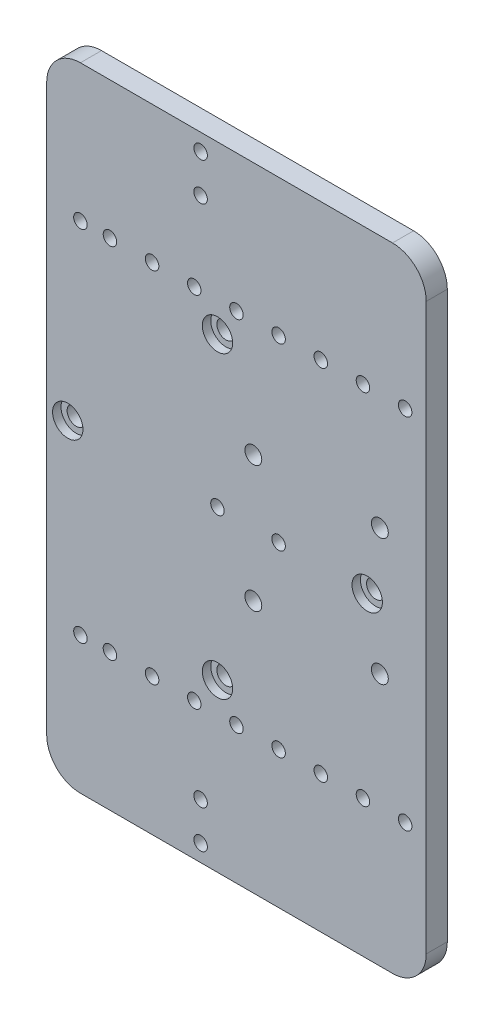
SolidWorks part; units mm, degrees
ref_plane "前视基准面" through (0, 0, 0) normal (0, 0, 1) x (1, 0, 0)
ref_plane "上视基准面" through (0, 0, 0) normal (0, 1, 0) x (1, 0, 0)
ref_plane "右视基准面" through (0, 0, 0) normal (1, 0, 0) x (0, 0, -1)
sketch "草图1" plane through (0, 0, 0) normal (0, 0, 1) x (1, 0, 0)
  line L1 (0, 0) -> (90, 0)
  line L2 (0, 0) -> (0, -150)
  line L3 (0, -150) -> (90, -150)
  line L4 (90, 0) -> (90, -150)
  circle A4 centre (79, -60) radius 2
  circle A5 centre (79, -90) radius 2
  circle A12 centre (49, -60) radius 2
  circle A13 centre (49, -90) radius 2
  circle A14 centre (40.5, -39.5) radius 2.15
  circle A15 centre (40.5, -110.5) radius 2.15
  circle A16 centre (76, -75) radius 2.15
  circle A17 centre (5, -75) radius 2.15
  circle A18 centre (85, -117.5) radius 1.6
  circle A19 centre (75, -117.5) radius 1.6
  circle A20 centre (65, -117.5) radius 1.6
  circle A21 centre (55, -117.5) radius 1.6
  circle A22 centre (45, -117.5) radius 1.6
  circle A23 centre (85, -32.5) radius 1.6
  circle A24 centre (75, -32.5) radius 1.6
  circle A25 centre (65, -32.5) radius 1.6
  circle A26 centre (55, -32.5) radius 1.6
  circle A27 centre (45, -32.5) radius 1.6
  circle A28 centre (35, -117.5) radius 1.6
  circle A29 centre (25, -117.5) radius 1.6
  circle A30 centre (15, -117.5) radius 1.6
  circle A31 centre (35, -32.5) radius 1.6
  circle A32 centre (25, -32.5) radius 1.6
  circle A33 centre (15, -32.5) radius 1.6
  circle A34 centre (8, -117.5) radius 1.6
  circle A35 centre (8, -32.5) radius 1.6
  circle A36 centre (36.5, -4) radius 1.6
  circle A37 centre (36.5, -13) radius 1.6
  circle A38 centre (36.5, -137) radius 1.6
  circle A39 centre (36.5, -146) radius 1.6
  circle A40 centre (55, -75) radius 1.6
  circle A41 centre (40.5, -75) radius 1.6
  dimension "D1" = 150
  dimension "D15" = 2
  dimension "D5" = 30
  dimension "D16" = 2
  dimension "D17" = 2
  dimension "D18" = 39.5
  dimension "D7" = 49
  dimension "D19" = 71
  dimension "D21" = 71
  dimension "D3" = 75
  dimension "D4" = 32.5
  dimension "D6" = 3.2
  dimension "D12" = 5
  dimension "D23" = 7
  dimension "D24" = 4
  dimension "D25" = 36.5
  dimension "D28" = 4
  dimension "D29" = 9
  dimension "D30" = 50
  dimension "D31" = 35.5
  dimension "D2" = 90
  dimension "D8" = 60
  dimension "D9" = 5
  dimension "D10" = 30
  dimension "D11" = 2
  dimension "D13" = 4
  dimension "D14" = 2
  dimension "D20" = 40.5
  dimension "D22" = 5
  dimension "D26" = 2
  dimension "D27" = 2
extrude "凸台-拉伸1" add sketch "草图1" along normal blind 5
fillet "圆角1" radius 8 4 edges at (0, -150, 2.5) (90, -150, 2.5) (90, 0, 2.5) (0, 0, 2.5)
sketch "草图2" plane through (0, 0, 5) normal (0, 0, 1) x (1, 0, 0)
  circle A0 centre (40.5, -39.5) radius 3.6
  circle A1 centre (76, -75) radius 3.6
  circle A2 centre (5, -75) radius 3.6
  circle A3 centre (40.5, -110.5) radius 3.6
  circle A5 centre (40.5, -39.5) radius 2.15 construction
  circle A6 centre (76, -75) radius 2.15 construction
  circle A7 centre (40.5, -110.5) radius 2.15 construction
  circle A8 centre (5, -75) radius 2.15 construction
extrude "切除-拉伸1" cut sketch "草图2" against normal blind 2
sketch "草图4" plane through (0, 0, 0) normal (0, 0, -1) x (-1, 0, 0)
  arc A0 (-42.1996, -35.0361) -> (-80.4639, -73.3004) centre (-40.5, -75) ccw
  arc A3 (-38.8004, -114.9639) -> (-42.1996, -114.9639) centre (-40.5, -110.5) ccw
  arc A4 (-80.4639, -76.6996) -> (-80.4639, -73.3004) centre (-76, -75) ccw
  arc A6 (-0.5361, -73.3004) -> (-0.5361, -76.6996) centre (-5, -75) ccw
  arc A7 (-42.1996, -35.0361) -> (-38.8004, -35.0361) centre (-40.5, -39.5) ccw
  arc A8 (-80.4639, -76.6996) -> (-42.1996, -114.9639) centre (-40.5, -75) ccw
  arc A9 (-38.8004, -114.9639) -> (-0.5361, -76.6996) centre (-40.5, -75) ccw
  arc A10 (-0.5361, -73.3004) -> (-38.8004, -35.0361) centre (-40.5, -75) ccw
  circle A11 centre (-40.5, -75) radius 30
extrude "凸台-拉伸2" add sketch "草图4" along normal blind 3
